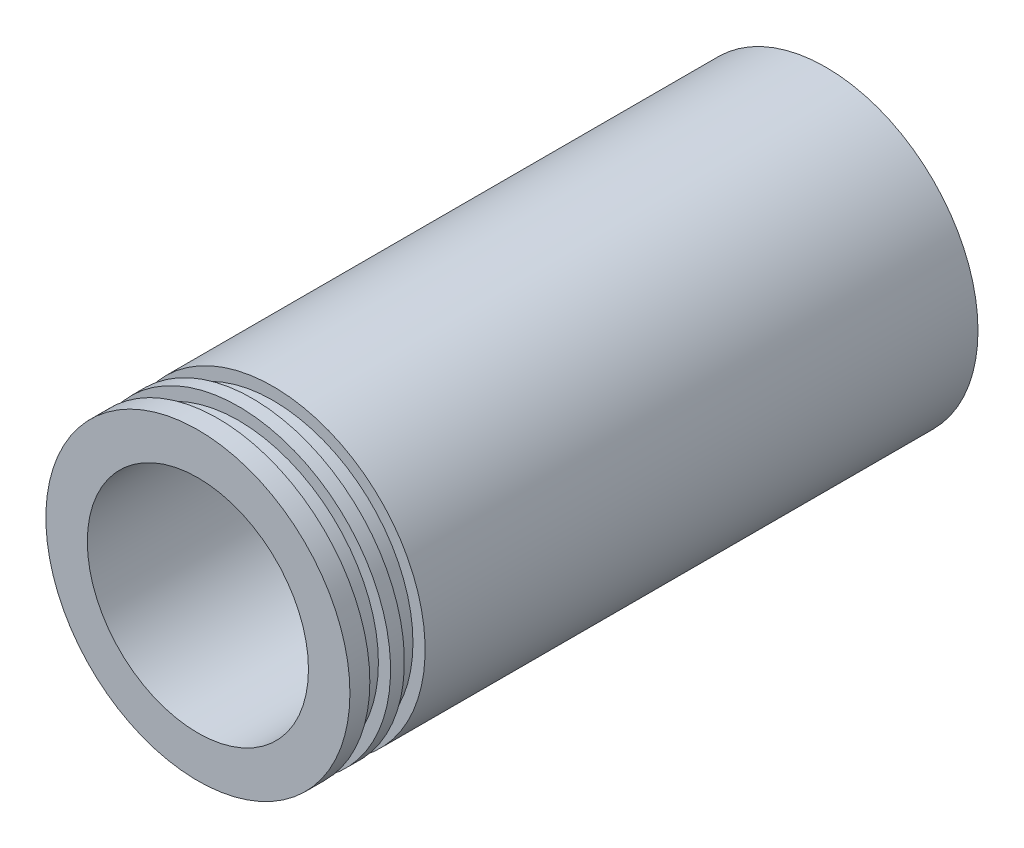
SolidWorks part; units mm, degrees
ref_plane "Front Plane" through (0, 0, 0) normal (0, 0, 1) x (1, 0, 0)
ref_plane "Top Plane" through (0, 0, 0) normal (0, 1, 0) x (1, 0, 0)
ref_plane "Right Plane" through (0, 0, 0) normal (1, 0, 0) x (0, 0, -1)
sketch "Sketch1" plane through (0, 0, 0) normal (0, 0, 1) x (1, 0, 0)
  circle A0 centre (0, 0) radius 34.925
  circle A1 centre (0, 0) radius 25.4
extrude "Boss-Extrude1" add sketch "Sketch1" along normal blind 144.272
sketch "groove" plane through (0, 0, 0) normal (1, 0, 0) x (0, 0, -1)
  line L0 (-139.7, 34.925) -> (-139.7, 32.131)
  line L1 (-139.7, 32.131) -> (-134.9375, 32.131)
  line L2 (-134.9375, 32.131) -> (-134.9375, 34.925)
  line L3 (-134.9375, 34.925) -> (-131.7625, 34.925)
  line L4 (-131.7625, 34.925) -> (-131.7625, 32.131)
  line L5 (-131.7625, 32.131) -> (-127, 32.131)
  line L6 (-127, 32.131) -> (-127, 34.925)
  line L7 (-139.7, 38.1) -> (-127, 38.1)
  line L8 (-127, 38.1) -> (-127, 34.925)
  line L9 (-139.7, 38.1) -> (-139.7, 34.925)
  line L10 (0, 34.925) -> (-144.272, 34.925) construction
  line L12 (0, -34.925) -> (0, 34.925) construction
  dimension "D1" = 2.794
  dimension "D2" = 2.794
  dimension "D3" = 4.7625
  dimension "D4" = 4.7625
  dimension "D5" = 127
  dimension "D6" = 12.7
  dimension "D7" = 3.175
ref_plane "Plane1" through (0, 0, 131.7625) normal (0, 0, 1) x (1, 0, 0)
sketch "groove path" plane through (0, 0, 131.7625) normal (0, 0, 1) x (1, 0, 0)
  circle A0 centre (0, 0) radius 34.925 construction
  circle A1 centre (0, 0) radius 34.925
sweep "Cut-Sweep1" cut profiles "groove" path "groove path"
